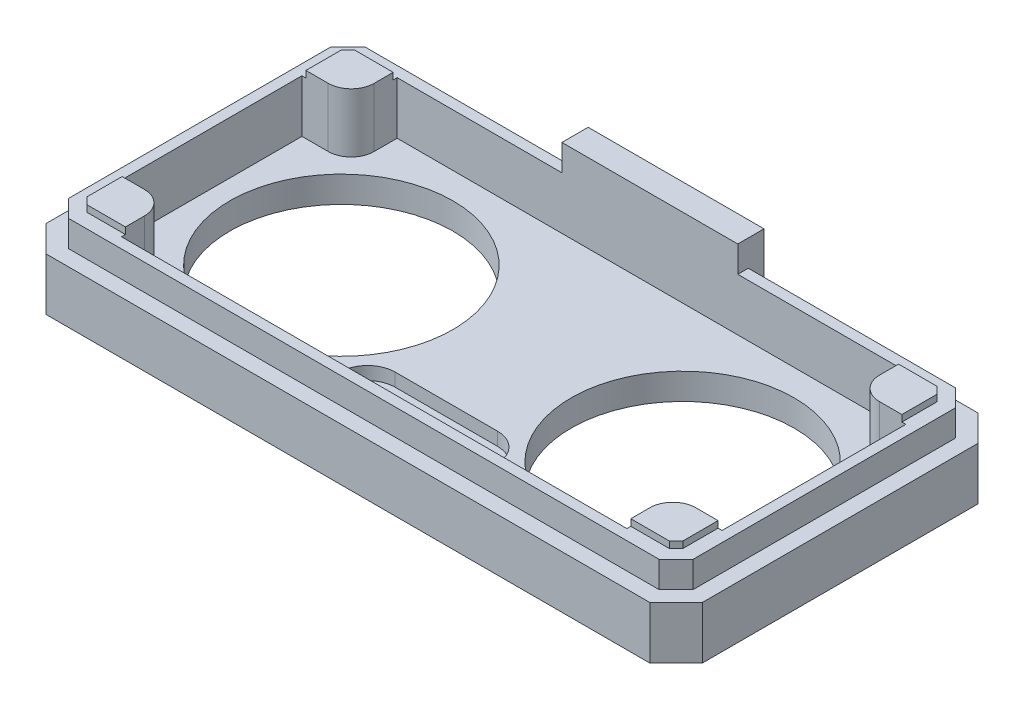
SolidWorks part; units mm, degrees
material "PLA+"
ref_plane "Front Plane" through (0, 0, 0) normal (0, 0, 1) x (1, 0, 0)
ref_plane "Top Plane" through (0, 0, 0) normal (0, 1, 0) x (1, 0, 0)
ref_plane "Right Plane" through (0, 0, 0) normal (1, 0, 0) x (0, 0, -1)
sketch "Sketch1" plane through (0, 0, 0) normal (0, 1, 0) x (1, 0, 0)
  line L0 (7, 12.5) -> (-23, 12.5)
  line L1 (23, 12.5) -> (7, 12.5)
  line L2 (25, 10.5) -> (25, -10.5)
  line L3 (23, -12.5) -> (-23, -12.5)
  line L4 (-25, 10.5) -> (-25, -10.5)
  line L5 (25, 12.5) -> (-25, -12.5) construction
  line L6 (25, -12.5) -> (-25, 12.5) construction
  line L7 (0, 0) -> (0, 11.0838) construction
  line L8 (-23, 12.5) -> (-25, 10.5)
  line L9 (-23, -12.5) -> (-25, -10.5)
  line L10 (25, -10.5) -> (23, -12.5)
  line L11 (25, 10.5) -> (23, 12.5)
  point P0 (0, 0)
  dimension "D1" = 50
  dimension "D2" = 25
extrude "Boss-Extrude1" add sketch "Sketch1" along normal blind 2
sketch "Sketch2" plane through (0, 2, 0) normal (0, 1, 0) x (1, 0, 0)
  line L0 (7.5, 12.5) -> (23, 12.5)
  line L1 (25, 10.5) -> (25, -10.5)
  line L2 (0, 0) -> (2.9968, 0) construction
  line L3 (23, -12.5) -> (0, -12.5)
  line L4 (-23, -12.5) -> (23, -12.5) construction
  line L5 (-1.4496, 10.5) -> (22.1716, 10.5)
  line L6 (23, 9.6716) -> (23, -9.6716)
  line L7 (22.1716, -10.5) -> (0, -10.5)
  line L8 (19.25, 8.75) -> (19.25, 10.5)
  line L9 (21, 7) -> (23, 7)
  line L10 (21, -7) -> (23, -7)
  line L11 (19.25, -8.75) -> (19.25, -10.5)
  line L12 (7.5, 10.5) -> (23, 10.5) construction
  line L13 (23, 12.5) -> (25, 10.5)
  line L14 (0, 0) -> (0, 2.3496) construction
  line L15 (-19.25, -8.75) -> (-19.25, -10.5)
  line L16 (-21, -7) -> (-23, -7)
  line L17 (-22.1716, -10.5) -> (0, -10.5)
  line L18 (-23, -12.5) -> (0, -12.5)
  line L19 (-21, 7) -> (-23, 7)
  line L20 (-19.25, 8.75) -> (-19.25, 10.5)
  line L21 (-23, 9.6716) -> (-23, -9.6716)
  line L22 (-25, 10.5) -> (-25, -10.5)
  line L23 (25, -10.5) -> (23, -12.5)
  line L24 (1.4496, 10.5) -> (-22.1716, 10.5)
  line L25 (-7.5, 12.5) -> (-23, 12.5)
  line L26 (-23, -12.5) -> (-25, -10.5)
  line L27 (-23, 12.5) -> (-25, 10.5)
  line L28 (-22.1716, 10.5) -> (-23, 9.6716)
  line L29 (22.1716, 10.5) -> (23, 9.6716)
  line L30 (23, -9.6716) -> (22.1716, -10.5)
  line L31 (-22.1716, -10.5) -> (-23, -9.6716)
  line L32 (-21.5858, -11.0858) -> (-23.5858, -9.0858) construction
  line L33 (-21.5858, 11.0858) -> (-23.5858, 9.0858) construction
  line L34 (7.5, 12.5) -> (25, 12.5) construction
  line L35 (25, 12.5) -> (25, -12.5) construction
  line L36 (21.5858, 11.0858) -> (23.5858, 9.0858) construction
  line L37 (23, 10.5) -> (23, -10.5) construction
  line L38 (25, -12.5) -> (0, -12.5) construction
  line L39 (23.5858, -9.0858) -> (21.5858, -11.0858) construction
  line L40 (23, -10.5) -> (0, -10.5) construction
  arc A0 (-21, -7) -> (-19.25, -8.75) centre (-21, -8.75) cw
  arc A1 (21, -7) -> (19.25, -8.75) centre (21, -8.75) ccw
  arc A2 (19.25, 8.75) -> (21, 7) centre (21, 8.75) ccw
  arc A3 (-19.25, 8.75) -> (-21, 7) centre (-21, 8.75) cw
  line M2 (-25, 10.5) -> (-25, -10.5)
  line M3 (-23, -12.5) -> (23, -12.5)
  line M4 (25, -10.5) -> (25, 10.5)
  line M5 (23, 12.5) -> (-23, 12.5)
  line M9 (23, 12.5) -> (-23, 12.5)
  dimension "D1" = 3.5
  dimension "D2" = 2
  dimension "D3" = 21
  dimension "D4" = 2
  dimension "D5" = 2
  dimension "D6" = 17.5
  dimension "D7" = 2
  dimension "D9" = 2
  dimension "D8" = 2
extrude "Boss-Extrude2" add sketch "Sketch2" along normal blind 4 contours L10 A1 L11 L7 L6 | L8 A2 L9 L6 L5 | A3 L20 L24 L21 L19 | A0 L16 L21 L17 L15 region at (-21.1602, 2, -8.782) region at (21.1602, 2, -8.782) region at (-21.1602, 2, 8.782) region at (21.1602, 2, 8.782)
extrude "Boss-Extrude3" add sketch "Sketch2<3>" along normal blind 4 contours L24 L5 L6 L7 L17 L21 M9 M2 M3 M4 M5 region at (15.25, 2, -11.941)
sketch "Sketch2<3>" plane through (0, 2, 0) normal (0, 1, 0) x (1, 0, 0) same geometry as "Sketch2"
sketch "Sketch3" plane through (0, 0, 0) normal (0, -1, 0) x (1, 0, 0)
  line L1 (0, 0) -> (0, 4.9492) construction
  circle A0 centre (-13, 0) radius 8.5
  circle A1 centre (13, 0) radius 8.5
  dimension "D1" = 17
  dimension "D3" = 26
extrude "ForSensors" cut sketch "Sketch3" against normal blind 5
sketch "Sketch4" plane through (0, 2, 0) normal (0, 1, 0) x (1, 0, 0)
  line L0 (3.9, -7.1) -> (-3.9, -7.1) construction
  line L1 (-19.25, -10.5) -> (19.25, -10.5) construction
  line L7 (3.9, -9.2) -> (-3.9, -9.2)
  line L8 (3.9, -5) -> (-3.9, -5)
  arc A0 (3.9, -9.2) -> (3.9, -5) centre (3.9, -7.1) ccw
  arc A1 (-3.9, -5) -> (-3.9, -9.2) centre (-3.9, -7.1) ccw
  point P1 (-6, -7.1)
  point P2 (6, -7.1)
  point P8 (0, -7.1)
  dimension "D1" = 4.2
  dimension "D2" = 12
  dimension "D3" = 3.4
extrude "ForCrystal" cut sketch "Sketch4" against normal blind 1
sketch "Sketch5" plane through (0, 6, 0) normal (0, 1, 0) x (1, 0, 0)
  line L0 (21, 7) -> (23, 7) construction
  line L1 (19.25, 8.75) -> (19.25, 10.5) construction
  line L2 (21, -7) -> (23, -7) construction
  line L3 (19.25, -8.75) -> (19.25, -10.5) construction
  line L4 (-19.25, 8.75) -> (-19.25, 10.5) construction
  line L5 (-19.25, -8.75) -> (-19.25, -10.5) construction
  line L6 (-21, -7) -> (-23, -7) construction
  line L7 (-19.25, 8.75) -> (-19.25, 10.5) construction
  line L8 (-21, 7) -> (-23, 7) construction
  line L9 (21, 7) -> (22.7, 7)
  line L10 (19.25, 8.75) -> (19.25, 10.2)
  line L11 (21, -7) -> (22.7, -7)
  line L12 (19.25, -8.75) -> (19.25, -10.2)
  line L13 (-19.25, 8.75) -> (-19.25, 10.2)
  line L14 (-19.25, -8.75) -> (-19.25, -10.2)
  line L15 (-21, -7) -> (-22.7, -7)
  line L16 (-19.25, 8.75) -> (-19.25, 10.2)
  line L17 (-21, 7) -> (-22.7, 7)
  line L18 (23, 7) -> (23, -7) construction
  line L19 (-22.7, 7) -> (-22.7, 9.6887)
  line L20 (-21.4444, 10.9444) -> (-23.4444, 8.9444)
  line L21 (-22.1887, 10.2) -> (-22.7, 9.6887)
  line L22 (-22.1887, 10.2) -> (-19.25, 10.2)
  line L23 (19.25, 10.5) -> (-19.25, 10.5) construction
  line L24 (-19.25, -10.5) -> (19.25, -10.5) construction
  line L25 (-23.4444, -8.9444) -> (-21.4444, -10.9444)
  line L26 (-22.7, -9.6887) -> (-22.1887, -10.2)
  line L27 (-23, 7) -> (-23, -7) construction
  line L28 (21.4444, -10.9444) -> (23.4444, -8.9444)
  line L29 (22.1887, -10.2) -> (22.7, -9.6887)
  line L30 (22.7, 7) -> (22.7, 9.6887)
  line L31 (23.4444, 8.9444) -> (21.4444, 10.9444)
  line L32 (22.7, 9.6887) -> (22.1887, 10.2)
  line L33 (19.25, 10.2) -> (22.1887, 10.2)
  line L34 (22.7, -7) -> (22.7, -9.6887)
  line L35 (19.25, -10.2) -> (22.1887, -10.2)
  line L36 (-22.7, -7) -> (-22.7, -9.6887)
  line L37 (-19.25, -10.2) -> (-22.1887, -10.2)
  arc A0 (19.25, 8.75) -> (21, 7) centre (21, 8.75) ccw construction
  arc A1 (21, -7) -> (19.25, -8.75) centre (21, -8.75) ccw construction
  arc A2 (-21, 7) -> (-19.25, 8.75) centre (-21, 8.75) ccw construction
  arc A3 (-19.25, -8.75) -> (-21, -7) centre (-21, -8.75) ccw construction
  arc A4 (-21, 7) -> (-19.25, 8.75) centre (-21, 8.75) ccw construction
  arc A5 (19.25, 8.75) -> (21, 7) centre (21, 8.75) ccw
  arc A6 (21, -7) -> (19.25, -8.75) centre (21, -8.75) ccw
  arc A7 (-21, 7) -> (-19.25, 8.75) centre (-21, 8.75) ccw
  arc A8 (-19.25, -8.75) -> (-21, -7) centre (-21, -8.75) ccw
  arc A9 (-21, 7) -> (-19.25, 8.75) centre (-21, 8.75) ccw
  line M2 (19.25, -8.75) -> (19.25, -10.5)
  line M4 (-19.25, -10.5) -> (-19.25, -8.75)
  arc M5 (-19.25, -8.75) -> (-21, -7) centre (-21, -8.75) ccw
  line M6 (-21, -7) -> (-23, -7)
  line M8 (-23, 7) -> (-21, 7)
  arc M9 (-21, 7) -> (-19.25, 8.75) centre (-21, 8.75) ccw
  line M10 (-19.25, 8.75) -> (-19.25, 10.5)
  line M12 (19.25, 10.5) -> (19.25, 8.75)
  arc M13 (19.25, 8.75) -> (21, 7) centre (21, 8.75) ccw
  line M14 (21, 7) -> (23, 7)
  line M16 (23, -7) -> (21, -7)
  arc M17 (21, -7) -> (19.25, -8.75) centre (21, -8.75) ccw
  dimension "D5" = 0.3
  dimension "D6" = 0.3
  dimension "D7" = 0.3
  dimension "D8" = 0.3
  dimension "D9" = 0.3
  dimension "D10" = 0.3
  dimension "D11" = 0.3
  dimension "D12" = 0.3
  dimension "D1" = 2.2
  dimension "D2" = 2.2
  dimension "D3" = 2.2
  dimension "D4" = 2.2
extrude "PcbLedge" add sketch "Sketch5" along normal blind 0.5 contours L22 L21 L19 M8 M9 M10 | L37 L36 L26 M4 M5 M6 | L33 L30 L32 M12 M13 M14 | L35 L29 L34 M2 M16 M17 region at (21.0407, 6, -8.6593) region at (21.0407, 6, 8.6593) region at (-21.0407, 6, -8.6593) region at (-21.0407, 6, 8.6593)
sketch "Sketch6" plane through (0, 6, 0) normal (0, 1, 0) x (1, 0, 0)
  line L0 (25, 10.5) -> (23, 12.5) construction
  line L1 (25, -10.5) -> (25, 10.5) construction
  line L2 (23, -12.5) -> (25, -10.5) construction
  line L3 (-23, -12.5) -> (23, -12.5) construction
  line L4 (-25, -10.5) -> (-23, -12.5) construction
  line L5 (-25, 10.5) -> (-25, -10.5) construction
  line L6 (-23, 12.5) -> (-25, 10.5) construction
  line L7 (23, 12.5) -> (-23, 12.5) construction
  line L8 (25, 10.5) -> (23, 12.5)
  line L9 (25, -10.5) -> (25, 10.5)
  line L10 (23, -12.5) -> (25, -10.5)
  line L11 (-23, -12.5) -> (23, -12.5)
  line L12 (-25, -10.5) -> (-23, -12.5)
  line L13 (-25, 10.5) -> (-25, -10.5)
  line L14 (-23, 12.5) -> (-25, 10.5)
  line L15 (23, 12.5) -> (6.7, 12.5)
  line L16 (22.5029, 11.3) -> (6.7, 11.3)
  line L17 (-22.5029, 11.3) -> (-23.8, 10.0029)
  line L18 (-23.8, 10.0029) -> (-23.8, -10.0029)
  line L19 (-23.8, -10.0029) -> (-22.5029, -11.3)
  line L20 (-22.5029, -11.3) -> (22.5029, -11.3)
  line L21 (22.5029, -11.3) -> (23.8, -10.0029)
  line L22 (23.8, -10.0029) -> (23.8, 10.0029)
  line L23 (23.8, 10.0029) -> (22.5029, 11.3)
  line L25 (0, 0) -> (0, 2.1517) construction
  line L26 (-6.7, 12.5) -> (-6.7, 11.3)
  line L28 (6.7, 12.5) -> (6.7, 11.3)
  line L29 (-6.7, 11.3) -> (-22.5029, 11.3)
  line L30 (22.5029, 11.3) -> (-22.5029, 11.3) construction
  line L31 (-6.7, 12.5) -> (-23, 12.5)
  line L32 (23, 12.5) -> (-23, 12.5) construction
  dimension "D2" = 13.4
  dimension "D1" = 1.2
extrude "Groove" cut sketch "Sketch6" against normal blind 2
sketch "Sketch7" plane through (0, 6, 0) normal (0, 1, 0) x (1, 0, 0)
  line L0 (6.7, 12.5) -> (6.7, 11.3) construction
  line L1 (-6.7, 11.3) -> (-6.7, 12.5) construction
  line L2 (6.7, 12.5) -> (-6.7, 12.5) construction
  line L3 (6.7, 12.5) -> (6.7, 10.5)
  line L4 (-6.7, 10.5) -> (-6.7, 12.5)
  line L5 (6.7, 12.5) -> (-6.7, 12.5)
  line L6 (19.25, 10.5) -> (-19.25, 10.5) construction
  line L7 (-6.7, 10.5) -> (6.7, 10.5)
extrude "Boss-Extrude5" add sketch "Sketch7" along normal blind 2
equation "\"D1@Sketch5\"= \"D4@Sketch5\""
equation "\"D2@Sketch5\"= \"D4@Sketch5\""
equation "\"D3@Sketch5\"= \"D4@Sketch5\""
equation "\"D6@Sketch5\"= \"D5@Sketch5\""
equation "\"D10@Sketch5\"= \"D5@Sketch5\""
equation "\"D9@Sketch5\"= \"D5@Sketch5\""
equation "\"D12@Sketch5\"= \"D5@Sketch5\""
equation "\"D11@Sketch5\"= \"D5@Sketch5\""
equation "\"D8@Sketch5\"= \"D5@Sketch5\""
equation "\"D7@Sketch5\"= \"D5@Sketch5\""
